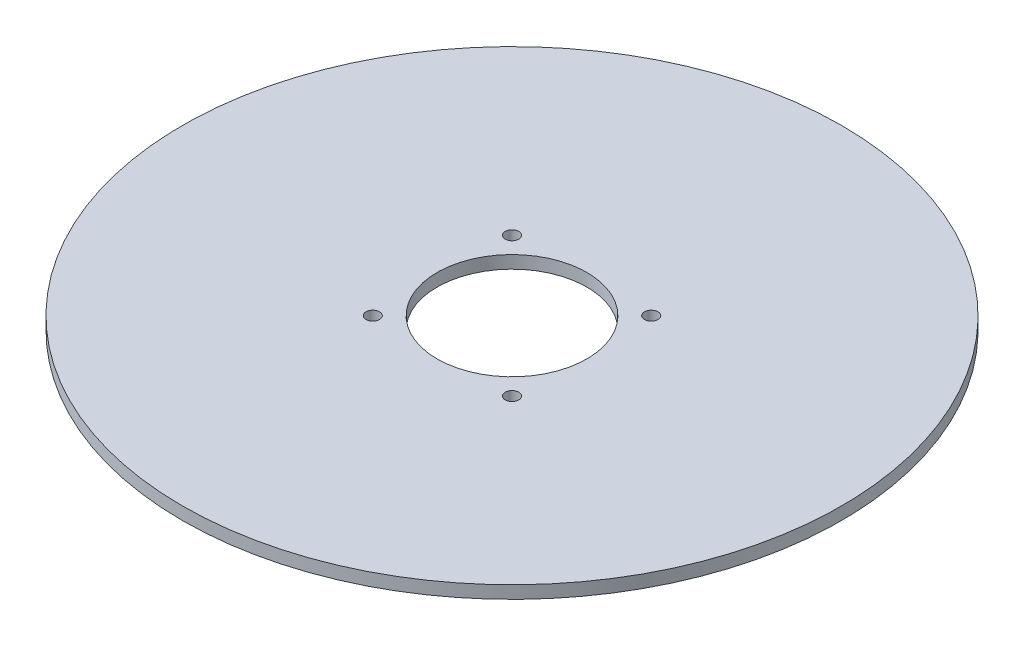
SolidWorks part; units mm, degrees
ref_plane "Front Plane" through (0, 0, 0) normal (0, 0, 1) x (1, 0, 0)
ref_plane "Top Plane" through (0, 0, 0) normal (0, 1, 0) x (1, 0, 0)
ref_plane "Right Plane" through (0, 0, 0) normal (1, 0, 0) x (0, 0, -1)
sketch "Sketch1" plane through (0, 0, 0) normal (0, 1, 0) x (1, 0, 0)
  circle A0 centre (0, 0) radius 165
  dimension "D1" = 330
extrude "Boss-Extrude1" add sketch "Sketch1" along normal blind 6.35
ref_axis "Axis1" through (0, 6.35, 0) along (0, -1, 0)
hole_wizard "1/4 Clearance Hole2" positions "Sketch4" profile "Sketch5" hole size "1/4" standard "ANSI Inch" end condition through all
sketch "Sketch4" plane through (0, 6.35, 0) normal (0, 1, 0) x (1, 0, 0)
  line L2 (34.85, -34.85) -> (-34.85, -34.85)
  line L3 (34.85, -34.85) -> (34.85, 34.85)
  line L4 (34.85, 34.85) -> (-34.85, 34.85)
  line L5 (-34.85, -34.85) -> (-34.85, 34.85)
  line L6 (34.85, -34.85) -> (-34.85, 34.85) construction
  line L7 (34.85, 34.85) -> (-34.85, -34.85) construction
  point P92 (-34.85, 34.85)
  point P145 (34.85, -34.85)
  point P146 (34.85, 34.85)
  point P147 (-34.85, -34.85)
  point P151 (0, 0)
  dimension "D1" = 69.7
sketch "Sketch5" plane through (-34.85, 6.35, -34.85) normal (1, 0, 0) x (0, 0, 1)
  line L0 (0, 0) -> (0, 6.35)
  line L1 (0, 6.35) -> (3.3782, 6.35)
  line L2 (3.3782, 6.35) -> (3.3782, 0)
  line L5 (3.3782, 0) -> (0, 0)
  line L11 (0, -6.35) -> (0, 107.95) construction
  dimension "Thru Hole Dia." = 6.7564
  dimension "Thru Hole Depth" = 6.35
sketch "Sketch6" plane through (0, 6.35, 0) normal (0, 1, 0) x (1, 0, 0)
  circle A0 centre (0, 0) radius 37.5
  dimension "D1" = 75
extrude "Cut-Extrude1" cut sketch "Sketch6" against normal through all
